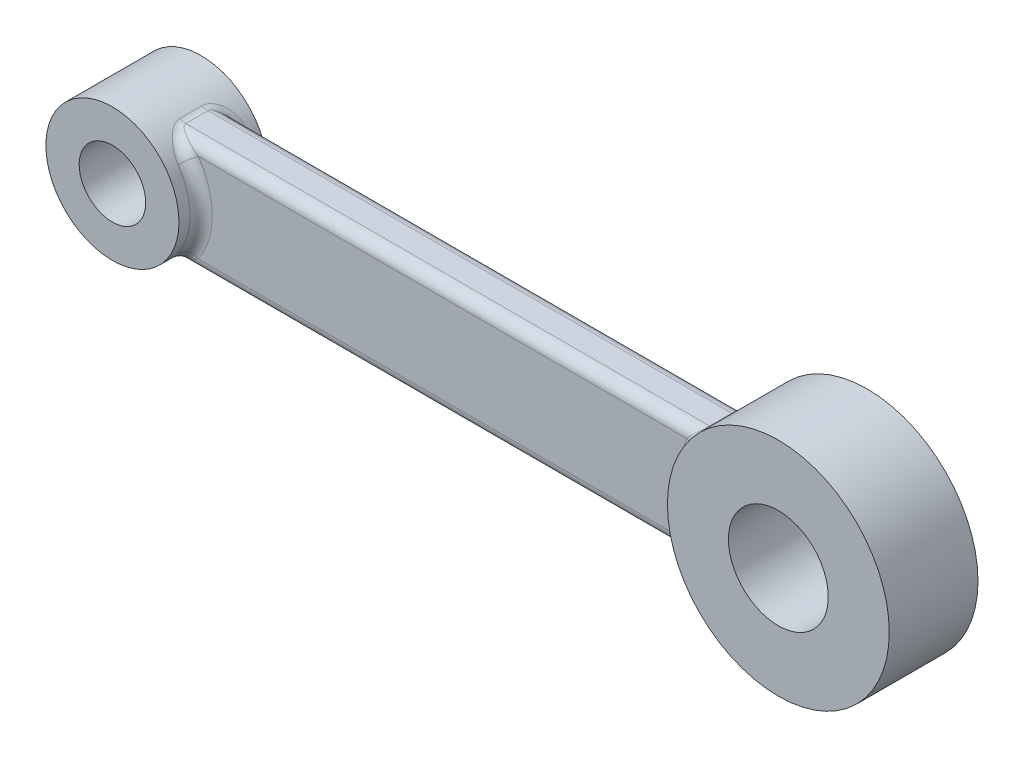
SolidWorks part; units mm, degrees
ref_plane "Front Plane" through (0, 0, 0) normal (0, 0, 1) x (1, 0, 0)
ref_plane "Top Plane" through (0, 0, 0) normal (0, 1, 0) x (1, 0, 0)
ref_plane "Right Plane" through (0, 0, 0) normal (1, 0, 0) x (0, 0, -1)
sketch "Sketch1" plane through (0, 0, 0) normal (0, 0, 1) x (1, 0, 0)
  line L1 (15, -2.5) -> (-15, -2.5)
  line L2 (15, -2.5) -> (15, 2.5)
  line L3 (15, 2.5) -> (-15, 2.5)
  line L4 (-15, -2.5) -> (-15, 2.5)
  line L5 (15, -2.5) -> (-15, 2.5) construction
  line L6 (15, 2.5) -> (-15, -2.5) construction
  point P0 (0, 0)
  dimension "D1" = 30
  dimension "D2" = 5
extrude "Boss-Extrude1" add sketch "Sketch1" along normal mid plane 2
sketch "Sketch4" plane through (0, 0, 0) normal (0, 0, 1) x (1, 0, 0)
  circle A0 centre (-14.8012, 0) radius 3
  circle A1 centre (15.2164, 0) radius 5
  dimension "D1" = 10
  dimension "D2" = 6
extrude "Boss-Extrude3" add sketch "Sketch4" along normal mid plane 4
sketch "Sketch5" plane through (0, 0, -2) normal (0, 0, -1) x (-1, 0, 0)
  circle A0 centre (14.8012, 0) radius 1.5
  circle A1 centre (-15.2164, 0) radius 2.25
  dimension "D1" = 3
  dimension "D2" = 4.5
extrude "Cut-Extrude1" cut sketch "Sketch5" against normal through all
fillet "Fillet1" radius 0.5 4 edges at (-1.1284, -2.5, 1) (-1.1284, -2.5, -1) (-1.1284, 2.5, 1) (-1.1284, 2.5, -1)
fillet "Fillet2" radius 0.5 16 edges at (10.8368, 2.4123, 0.7829) (10.8862, 2.5, 0) (10.8368, -2.4123, -0.7829) (10.8862, -2.5, 0) (10.7964, -2.3376, 0.8688) (10.2164, 0, 1) (10.7964, 2.3376, -0.8688) (10.2164, 0, -1) (-13.0775, -2.4553, 0.7066) (-13.1429, -2.5, 0) (-13.0775, 2.4553, -0.7066) (-13.1429, 2.5, 0) (-12.9993, 2.3986, 0.8019) (-11.8012, 0, 1) (-12.9993, -2.3986, -0.8019) (-11.8012, 0, -1)
